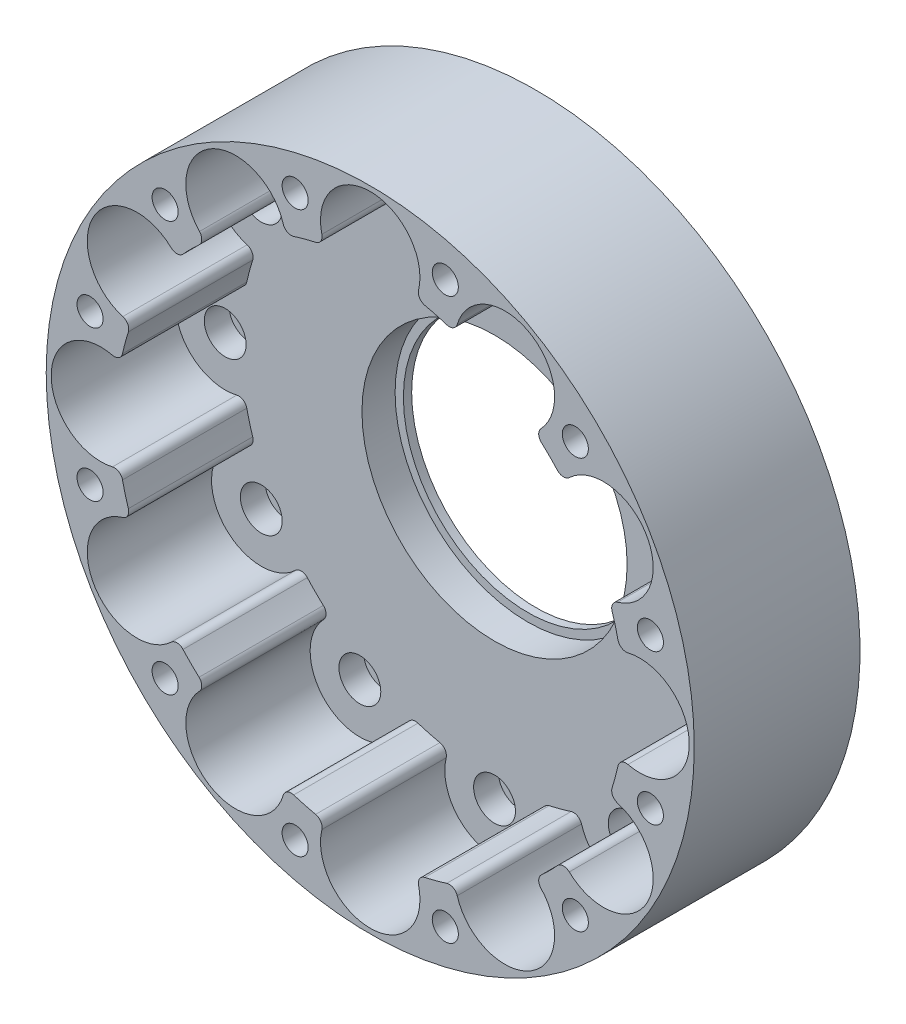
SolidWorks part; units mm, degrees
material "ABS"
ref_plane "Front Plane" through (0, 0, 0) normal (0, 0, 1) x (1, 0, 0)
ref_plane "Top Plane" through (0, 0, 0) normal (0, 1, 0) x (1, 0, 0)
ref_plane "Right Plane" through (0, 0, 0) normal (1, 0, 0) x (0, 0, -1)
sketch "Sketch1" plane through (0, 0, 0) normal (0, 0, 1) x (1, 0, 0)
  circle A0 centre (0, 0) radius 39.1
  circle A1 centre (0, 0) radius 32.5 construction
  circle A2 centre (32.5, 0) radius 2.525
  circle A3 centre (28.1458, -16.25) radius 2.525
  circle A4 centre (16.25, -28.1458) radius 2.525
  circle A5 centre (0, -32.5) radius 2.525
  circle A6 centre (-16.25, -28.1458) radius 2.525
  circle A7 centre (-28.1458, -16.25) radius 2.525
  circle A8 centre (-32.5, 0) radius 2.525
  circle A9 centre (-28.1458, 16.25) radius 2.525
  circle A10 centre (-16.25, 28.1458) radius 2.525
  circle A11 centre (0, 32.5) radius 2.525
  circle A12 centre (16.25, 28.1458) radius 2.525
  circle A13 centre (0, 0) radius 16
  circle A14 centre (28.1458, 16.25) radius 2.525
  point P28 (0, 0)
extrude "Boss-Extrude1" add sketch "Sketch1" along normal blind 3
sketch "Sketch2" plane through (0, 0, 0) normal (0, 0, -1) x (-1, 0, 0)
  circle A0 centre (0, 0) radius 16
  circle A1 centre (0, 0) radius 39.1
  circle A2 centre (0, 0) radius 39.1 construction
  dimension "D1" = 32
extrude "Boss-Extrude2" add sketch "Sketch2" along normal blind 2 contours A1 | A0
sketch "Sketch3" plane through (0, 0, 3) normal (0, 0, 1) x (1, 0, 0)
  circle A0 centre (32.5, 0) radius 1.6
  circle A1 centre (28.1458, -16.25) radius 1.6
  circle A2 centre (16.25, -28.1458) radius 1.6
  circle A3 centre (0, -32.5) radius 1.6
  circle A4 centre (-16.25, -28.1458) radius 1.6
  circle A5 centre (-28.1458, -16.25) radius 1.6
  circle A6 centre (-32.5, 0) radius 1.6
  circle A7 centre (-28.1458, 16.25) radius 1.6
  circle A8 centre (-16.25, 28.1458) radius 1.6
  circle A9 centre (0, 32.5) radius 1.6
  circle A10 centre (16.25, 28.1458) radius 1.6
  circle A11 centre (28.1458, 16.25) radius 1.6
  point P25 (0, 0)
  dimension "D1" = 3.2
  dimension "D2" = 12
sketch "Sketch4" plane through (0, 0, -2) normal (0, 0, -1) x (-1, 0, 0)
  circle A0 centre (0, 0) radius 16
  circle A1 centre (0, 0) radius 15
  dimension "D1" = 32
  dimension "D2" = 30
extrude "Boss-Extrude3" add sketch "Sketch4" against normal blind 1
sketch "Sketch5" plane through (0, 0, 3) normal (0, 0, 1) x (1, 0, 0)
  circle A0 centre (0, 0) radius 39.1
  circle A1 centre (0, 0) radius 39.1 construction
  arc A2 (-10.289, 28.8292) -> (-19.8223, 23.3251) centre (-16.25, 28.1458) ccw
  arc A3 (5.504, 30.1113) -> (-5.504, 30.1113) centre (0, 32.5) ccw
  arc A4 (19.8223, 23.3251) -> (10.289, 28.8292) centre (16.25, 28.1458) ccw
  arc A5 (28.8292, 10.289) -> (23.3251, 19.8223) centre (28.1458, 16.25) ccw
  arc A6 (30.1113, -5.504) -> (30.1113, 5.504) centre (32.5, 0) ccw
  arc A7 (23.3251, -19.8223) -> (28.8292, -10.289) centre (28.1458, -16.25) ccw
  arc A8 (10.289, -28.8292) -> (19.8223, -23.3251) centre (16.25, -28.1458) ccw
  arc A9 (-5.504, -30.1113) -> (5.504, -30.1113) centre (0, -32.5) ccw
  arc A10 (-19.8223, -23.3251) -> (-10.289, -28.8292) centre (-16.25, -28.1458) ccw
  arc A11 (-28.8292, -10.289) -> (-23.3251, -19.8223) centre (-28.1458, -16.25) ccw
  arc A12 (-30.1113, 5.504) -> (-30.1113, -5.504) centre (-32.5, 0) ccw
  arc A13 (-23.3251, -19.8223) -> (-19.8223, -23.3251) centre (0, 0) ccw
  arc A14 (-30.1113, -5.504) -> (-28.8292, -10.289) centre (0, 0) ccw
  arc A15 (-19.8223, 23.3251) -> (-23.3251, 19.8223) centre (0, 0) ccw
  arc A16 (-5.504, 30.1113) -> (-10.289, 28.8292) centre (0, 0) ccw
  arc A17 (10.289, 28.8292) -> (5.504, 30.1113) centre (0, 0) ccw
  arc A18 (23.3251, 19.8223) -> (19.8223, 23.3251) centre (0, 0) ccw
  arc A19 (30.1113, 5.504) -> (28.8292, 10.289) centre (0, 0) ccw
  arc A20 (28.8292, -10.289) -> (30.1113, -5.504) centre (0, 0) ccw
  arc A21 (19.8223, -23.3251) -> (23.3251, -19.8223) centre (0, 0) ccw
  arc A22 (5.504, -30.1113) -> (10.289, -28.8292) centre (0, 0) ccw
  arc A23 (-10.289, -28.8292) -> (-5.504, -30.1113) centre (0, 0) ccw
  arc A24 (-23.3251, 19.8223) -> (-28.8292, 10.289) centre (-28.1458, 16.25) ccw
  arc A25 (-28.8292, 10.289) -> (-30.1113, 5.504) centre (0, 0) ccw
  point P30 (0, 0)
  dimension "D1" = 12
  dimension "D2" = 6
extrude "Boss-Extrude4" add sketch "Sketch5" along normal blind 15 contours A24 A15 A2 A0 | A16 A3 A0 A2 | A17 A4 A0 A3 | A18 A5 A0 A4 | A19 A6 A0 A5 | A20 A7 A0 A6 | A21 A8 A0 A7 | A22 A9 A0 A8 | A23 A10 A0 A9 | A13 A11 A0 A10 | A14 A12 A0 A11 | A24 A0 A12 A15 region at (-38.9894, 0, 3)
fillet "Fillet2" radius 1 24 edges at (10.289, -28.8292, 10.5) (5.504, -30.1113, 10.5) (30.1113, -5.504, 10.5) (28.8292, -10.289, 10.5) (23.3251, -19.8223, 10.5) (19.8223, -23.3251, 10.5) (-10.289, -28.8292, 10.5) (-5.504, -30.1113, 10.5) (-19.8223, -23.3251, 10.5) (-23.3251, -19.8223, 10.5) (-30.1113, -5.504, 10.5) (-28.8292, -10.289, 10.5) (-19.8223, 23.3251, 10.5) (30.1113, 5.504, 10.5) (28.8292, 10.289, 10.5) (23.3251, 19.8223, 10.5) (19.8223, 23.3251, 10.5) (10.289, 28.8292, 10.5) (5.504, 30.1113, 10.5) (-5.504, 30.1113, 10.5) (-10.289, 28.8292, 10.5) (-30.1113, 5.504, 10.5) (-28.8292, 10.289, 10.5) (-23.3251, 19.8223, 10.5)
sketch "Sketch7" plane through (0, 0, -2) normal (0, 0, -1) x (-1, 0, 0)
  line L0 (0, 0) -> (33.8074, -9.0587) construction
  line L1 (0, 0) -> (35, 0) construction
  circle A0 centre (33.8074, -9.0587) radius 1.575
  circle A1 centre (24.7487, -24.7487) radius 1.575
  circle A2 centre (9.0587, -33.8074) radius 1.575
  circle A3 centre (-9.0587, -33.8074) radius 1.575
  circle A4 centre (-24.7487, -24.7487) radius 1.575
  circle A5 centre (-33.8074, -9.0587) radius 1.575
  circle A6 centre (-33.8074, 9.0587) radius 1.575
  circle A7 centre (-24.7487, 24.7487) radius 1.575
  circle A8 centre (-9.0587, 33.8074) radius 1.575
  circle A9 centre (9.0587, 33.8074) radius 1.575
  circle A10 centre (24.7487, 24.7487) radius 1.575
  circle A11 centre (33.8074, 9.0587) radius 1.575
  point P5 (0, 0)
  point P6 (0, 0)
  point P26 (0, 0)
  point P30 (0, 0)
  point P31 (0, 0)
  point P32 (0, 0)
  point P33 (0, 0)
  point P34 (0, 0)
  point P35 (0, 0)
  point P36 (0, 0)
  point P37 (0, 0)
  point P38 (0, 0)
  point P39 (0, 0)
  point P40 (0, 0)
  point P41 (0, 0)
  point P42 (0, 0)
  point P43 (0, 0)
  point P44 (0, 0)
  point P45 (0, 0)
  point P46 (0, 0)
  point P47 (33.8074, 9.0587)
  dimension "D2" = 3.15
  dimension "D4" = 35
  dimension "D5" = 15
  dimension "D3" = 12
extrude "Cut-Extrude1" cut sketch "Sketch7" against normal through all
sketch "Sketch8" plane through (0, 0, -2) normal (0, 0, -1) x (-1, 0, 0)
  line L0 (27.5987, -26.3942) -> (27.5987, -23.1033)
  line L1 (37.0983, -9.0587) -> (35.4529, -6.2087)
  line L2 (35.4529, -6.2087) -> (32.162, -6.2087)
  line L3 (32.162, -6.2087) -> (30.5165, -9.0587)
  line L4 (30.5165, -9.0587) -> (32.162, -11.9087)
  line L5 (32.162, -11.9087) -> (35.4529, -11.9087)
  line L6 (35.4529, -11.9087) -> (37.0983, -9.0587)
  line L7 (27.5987, -23.1033) -> (24.7487, -21.4578)
  line L8 (24.7487, -21.4578) -> (21.8987, -23.1033)
  line L9 (21.8987, -23.1033) -> (21.8987, -26.3942)
  line L10 (21.8987, -26.3942) -> (24.7487, -28.0396)
  line L11 (24.7487, -28.0396) -> (27.5987, -26.3942)
  line L12 (10.7041, -36.6574) -> (12.3496, -33.8074)
  line L13 (12.3496, -33.8074) -> (10.7041, -30.9574)
  line L14 (10.7041, -30.9574) -> (7.4132, -30.9574)
  line L15 (7.4132, -30.9574) -> (5.7678, -33.8074)
  line L16 (5.7678, -33.8074) -> (7.4132, -36.6574)
  line L17 (7.4132, -36.6574) -> (10.7041, -36.6574)
  line L18 (-9.0587, -37.0983) -> (-6.2087, -35.4529)
  line L19 (-6.2087, -35.4529) -> (-6.2087, -32.162)
  line L20 (-6.2087, -32.162) -> (-9.0587, -30.5165)
  line L21 (-9.0587, -30.5165) -> (-11.9087, -32.162)
  line L22 (-11.9087, -32.162) -> (-11.9087, -35.4529)
  line L23 (-11.9087, -35.4529) -> (-9.0587, -37.0983)
  line L24 (-26.3942, -27.5987) -> (-23.1033, -27.5987)
  line L25 (-23.1033, -27.5987) -> (-21.4578, -24.7487)
  line L26 (-21.4578, -24.7487) -> (-23.1033, -21.8987)
  line L27 (-23.1033, -21.8987) -> (-26.3942, -21.8987)
  line L28 (-26.3942, -21.8987) -> (-28.0396, -24.7487)
  line L29 (-28.0396, -24.7487) -> (-26.3942, -27.5987)
  line L30 (-36.6574, -10.7041) -> (-33.8074, -12.3496)
  line L31 (-33.8074, -12.3496) -> (-30.9574, -10.7041)
  line L32 (-30.9574, -10.7041) -> (-30.9574, -7.4132)
  line L33 (-30.9574, -7.4132) -> (-33.8074, -5.7678)
  line L34 (-33.8074, -5.7678) -> (-36.6574, -7.4132)
  line L35 (-36.6574, -7.4132) -> (-36.6574, -10.7041)
  line L36 (-37.0983, 9.0587) -> (-35.4529, 6.2087)
  line L37 (-35.4529, 6.2087) -> (-32.162, 6.2087)
  line L38 (-32.162, 6.2087) -> (-30.5165, 9.0587)
  line L39 (-30.5165, 9.0587) -> (-32.162, 11.9087)
  line L40 (-32.162, 11.9087) -> (-35.4529, 11.9087)
  line L41 (-35.4529, 11.9087) -> (-37.0983, 9.0587)
  line L42 (-27.5987, 26.3942) -> (-27.5987, 23.1033)
  line L43 (-27.5987, 23.1033) -> (-24.7487, 21.4578)
  line L44 (-24.7487, 21.4578) -> (-21.8987, 23.1033)
  line L45 (-21.8987, 23.1033) -> (-21.8987, 26.3942)
  line L46 (-21.8987, 26.3942) -> (-24.7487, 28.0396)
  line L47 (-24.7487, 28.0396) -> (-27.5987, 26.3942)
  line L48 (-10.7041, 36.6574) -> (-12.3496, 33.8074)
  line L49 (-12.3496, 33.8074) -> (-10.7041, 30.9574)
  line L50 (-10.7041, 30.9574) -> (-7.4132, 30.9574)
  line L51 (-7.4132, 30.9574) -> (-5.7678, 33.8074)
  line L52 (-5.7678, 33.8074) -> (-7.4132, 36.6574)
  line L53 (-7.4132, 36.6574) -> (-10.7041, 36.6574)
  line L54 (9.0587, 37.0983) -> (6.2087, 35.4529)
  line L55 (6.2087, 35.4529) -> (6.2087, 32.162)
  line L56 (6.2087, 32.162) -> (9.0587, 30.5165)
  line L57 (9.0587, 30.5165) -> (11.9087, 32.162)
  line L58 (11.9087, 32.162) -> (11.9087, 35.4529)
  line L59 (11.9087, 35.4529) -> (9.0587, 37.0983)
  line L60 (26.3942, 27.5987) -> (23.1033, 27.5987)
  line L61 (23.1033, 27.5987) -> (21.4578, 24.7487)
  line L62 (21.4578, 24.7487) -> (23.1033, 21.8987)
  line L63 (23.1033, 21.8987) -> (26.3942, 21.8987)
  line L64 (26.3942, 21.8987) -> (28.0396, 24.7487)
  line L65 (28.0396, 24.7487) -> (26.3942, 27.5987)
  line L66 (36.6574, 10.7041) -> (33.8074, 12.3496)
  line L67 (33.8074, 12.3496) -> (30.9574, 10.7041)
  line L68 (30.9574, 10.7041) -> (30.9574, 7.4132)
  line L69 (30.9574, 7.4132) -> (33.8074, 5.7678)
  line L70 (33.8074, 5.7678) -> (36.6574, 7.4132)
  line L71 (36.6574, 7.4132) -> (36.6574, 10.7041)
  circle A0 centre (33.8074, -9.0587) radius 2.85 construction
  circle A1 centre (24.7487, -24.7487) radius 2.85 construction
  circle A2 centre (9.0587, -33.8074) radius 2.85 construction
  circle A3 centre (-9.0587, -33.8074) radius 2.85 construction
  circle A4 centre (-24.7487, -24.7487) radius 2.85 construction
  circle A5 centre (-33.8074, -9.0587) radius 2.85 construction
  circle A6 centre (-33.8074, 9.0587) radius 2.85 construction
  circle A7 centre (-24.7487, 24.7487) radius 2.85 construction
  circle A8 centre (-9.0587, 33.8074) radius 2.85 construction
  circle A9 centre (9.0587, 33.8074) radius 2.85 construction
  circle A10 centre (24.7487, 24.7487) radius 2.85 construction
  circle A11 centre (33.8074, 9.0587) radius 2.85 construction
  point P91 (0, 0)
  dimension "D1" = 5.7
  dimension "D2" = 12
extrude "Cut-Extrude3" cut sketch "Sketch8" against normal blind 3
sketch "Sketch9" plane through (0, 0, 3) normal (0, 0, 1) x (1, 0, 0)
  circle A0 centre (0, 0) radius 39.1
  circle A1 centre (0, 0) radius 38.5
  dimension "D1" = 77
equation "\"RingPinShaft\"= 5.05"
equation "\"CenterBearingOut\"=32.00"
equation "\"OutputBearingOut\"=37.00"
equation "\"RingPostIn\"=5.15"
equation "\"CamBearingOut\"=15.1"
equation "\"DiskOutputShaft\"=10.1"
equation "\"CenterShaft\"=25.2"
equation "\"Eccentricity\"=2"
equation "\"CycCamShaft\"=10.05"
equation "\"m3Thru\"=3.15"
equation "\"m3Insert\"=4.2"
equation "\"MountingHoleDiam\"=35"
equation "\"D2@Sketch7\"=\"m3Thru\""
equation "\"D4@Sketch7\"=\"MountingHoleDiam\""
